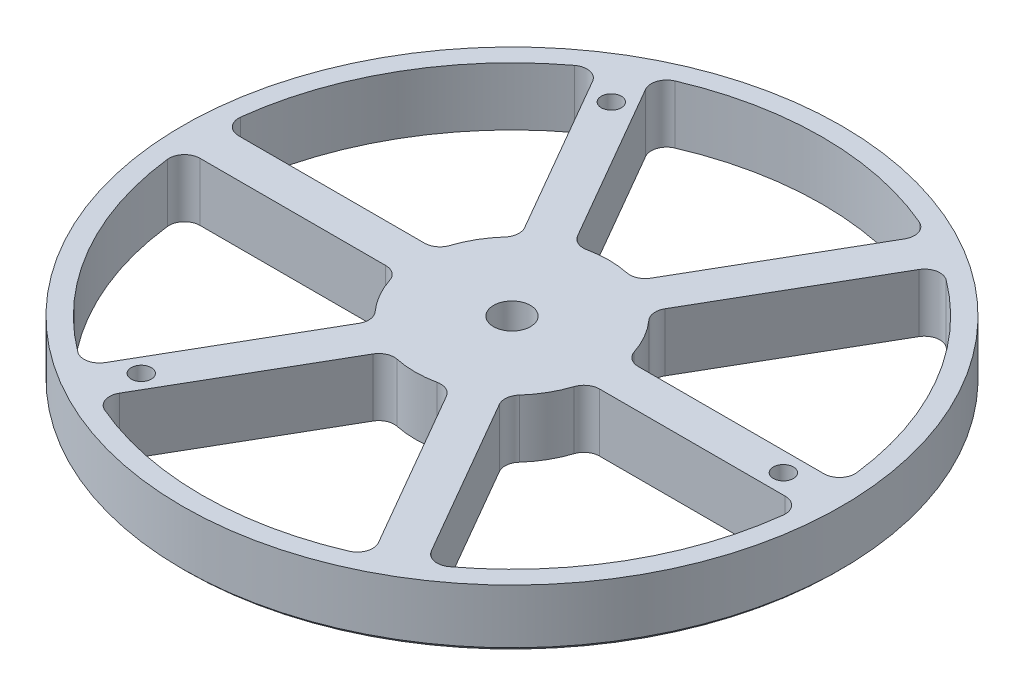
SolidWorks part; units mm, degrees
ref_plane "Front Plane" through (0, 0, 0) normal (0, 0, 1) x (1, 0, 0)
ref_plane "Top Plane" through (0, 0, 0) normal (0, 1, 0) x (1, 0, 0)
ref_plane "Right Plane" through (0, 0, 0) normal (1, 0, 0) x (0, 0, -1)
sketch "Sketch2" plane through (0, 0, 0) normal (1, 0, 0) x (0, 0, -1)
  line L0 (0, 0) -> (-84.9998, 0)
  line L1 (-84.9998, 0) -> (-84.9998, 15)
  line L2 (-84.9998, 15) -> (0, 15)
  line L5 (0, 15) -> (0, 0)
  dimension "D1" = 84.9998
  dimension "D2" = 15
ref_axis "Axis1" through (0, -0.75, 0) along (0, 1, 0)
revolve "Revolve1" add sketch "Sketch2" angle 360 about axis through (0, -0.75, 0) along (0, 1, 0)
hole_wizard "#6 (0.204) Diameter Hole1" positions "Sketch6" profile "Sketch7" hole size "#6" standard "ANSI Inch" end condition through all
sketch "Sketch6" plane through (0, 15, 0) normal (0, 1, 0) x (1, 0, 0)
  line L0 (0, 0) -> (-69.8201, 120.932) construction
  line L2 (0, 0) -> (0, 109.0908) construction
  point P0 (-35, 60.6218)
  dimension "D1" = 30
  dimension "D2" = 70
sketch "Sketch7" plane through (-35, 15, -60.6218) normal (1, 0, 0) x (0, 0, 1)
  line L0 (0, 0) -> (0, 15)
  line L1 (0, 15) -> (2.5908, 15)
  line L2 (2.5908, 15) -> (2.5908, 0)
  line L5 (2.5908, 0) -> (0, 0)
  line L11 (0, -6.35) -> (0, 107.95) construction
  dimension "Thru Hole Dia." = 5.1816
  dimension "Thru Hole Depth" = 15
pattern_circular "CirPattern3" count 3 over 360 about axis through (0, -0.75, 0) along (0, 1, 0) of "#6 (0.204) Diameter Hole1"
sketch "Sketch8" plane through (0, 15, 0) normal (0, 1, 0) x (1, 0, 0)
  line L4 (0, 0) -> (0, 93.9995) construction
  line L5 (0, 0) -> (113.8372, 0) construction
  line L6 (-7.9173, 23.7132) -> (-35.5916, 71.6464)
  line L7 (7.9173, 23.7132) -> (35.5916, 71.6464)
  line L8 (0, 0) -> (-35, 60.6218) construction
  arc A0 (-7.9173, 23.7132) -> (7.9173, 23.7132) centre (0, 0) cw
  arc A1 (-35.5916, 71.6464) -> (35.5916, 71.6464) centre (0, 0) cw
  circle A2 centre (0, 0) radius 84.9998 construction
  dimension "D1" = 25
  dimension "D2" = 5
  dimension "D3" = 5
extrude "Cut-Extrude1" cut sketch "Sketch8" against normal through all
fillet "Fillet1" radius 4 4 edges at (7.9173, 7.5, -23.7132) (35.5916, 7.5, -71.6464) (-7.9173, 7.5, -23.7132) (-35.5916, 7.5, -71.6464)
pattern_circular "CirPattern4" count 6 over 360 about axis through (0, -0.75, 0) along (0, 1, 0) of "Cut-Extrude1", "Fillet1"
chamfer "Chamfer2" distance 1 angle 45 1 edges at (0, 0, -84.9998)
hole_wizard "3/8 (0.375) Diameter Hole1" positions "Sketch9" profile "Sketch11" hole size "3/8" standard "ANSI Inch" end condition through all
sketch "Sketch9" plane through (0, 0, 0) normal (0, -1, 0) x (-1, 0, 0)
  point P0 (0, 0)
sketch "Sketch11" plane through (0, 0, 0) normal (1, 0, 0) x (0, 0, -1)
  line L0 (0, 0) -> (0, 15)
  line L1 (0, 15) -> (4.7625, 15)
  line L2 (4.7625, 15) -> (4.7625, 0)
  line L5 (4.7625, 0) -> (0, 0)
  line L11 (0, -6.35) -> (0, 107.95) construction
  dimension "Thru Hole Dia." = 9.525
  dimension "Thru Hole Depth" = 15
